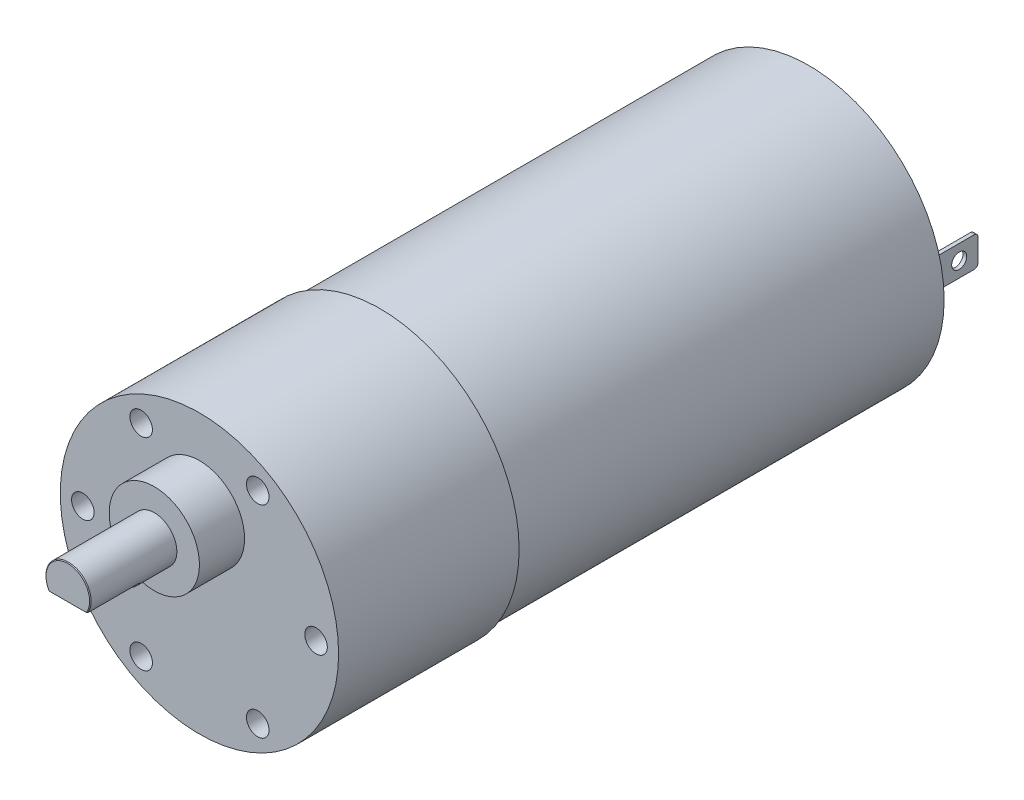
SolidWorks part; units mm, degrees
ref_plane "前视基准面" through (0, 0, 0) normal (0, 0, 1) x (1, 0, 0)
ref_plane "上视基准面" through (0, 0, 0) normal (0, 1, 0) x (1, 0, 0)
ref_plane "右视基准面" through (0, 0, 0) normal (1, 0, 0) x (0, 0, -1)
sketch "草图1" plane through (0, 0, 0) normal (0, 0, 1) x (1, 0, 0)
  circle A0 centre (0, 0) radius 18.5
  dimension "D1" = 37
extrude "凸台-拉伸1" add sketch "草图1" along normal blind 24
sketch "草图2" plane through (0, 0, 24) normal (0, 0, 1) x (1, 0, 0)
  circle A0 centre (0, 7) radius 6
  dimension "D2" = 12
  dimension "D1" = 7
extrude "凸台-拉伸2" add sketch "草图2" along normal blind 6
sketch "草图3" plane through (0, 0, 24) normal (0, 0, 1) x (1, 0, 0)
  circle A1 centre (15.5, 0) radius 1.5
  dimension "D1" = 3
  dimension "D2" = 15.5
extrude "切除-拉伸1" cut sketch "草图3" against normal blind 4
sketch "草图4" plane through (0, 0, 30) normal (0, 0, 1) x (1, 0, 0)
  circle A0 centre (0, 7) radius 3
  dimension "D1" = 6
extrude "凸台-拉伸3" add sketch "草图4" along normal blind 11.5
chamfer "倒角1" distance 0.1 angle 45 1 edges at (3, 7, 41.5)
sketch "草图5" plane through (0, 0, 41.5) normal (0, 0, 1) x (1, 0, 0)
  line L2 (-2.5897, 5.4856) -> (2.5897, 5.4856)
  circle A0 centre (0, 7) radius 3 construction
  arc A3 (-2.5897, 5.4856) -> (2.5897, 5.4856) centre (0, 7) ccw
extrude "切除-拉伸2" cut sketch "草图5" against normal blind 7
ref_axis "基准轴1" through (0, 0, 47.25) along (0, 0, -1)
pattern_circular "阵列(圆周)1" count 6 over 360 about axis through (0, 0, 47.25) along (0, 0, -1) of "切除-拉伸1"
sketch "草图6" plane through (0, 0, 0) normal (0, 0, -1) x (-1, 0, 0)
  circle A0 centre (0, 0) radius 18
  dimension "D1" = 36
extrude "凸台-拉伸4" add sketch "草图6" along normal blind 57
sketch "草图7" plane through (0, 0, -57) normal (0, 0, -1) x (-1, 0, 0)
  circle A0 centre (0, 0) radius 6.5
  dimension "D1" = 13
extrude "凸台-拉伸5" add sketch "草图7" along normal blind 3.5
fillet "圆角1" radius 1 1 edges at (-6.5, 0, -60.5)
sketch "草图8" plane through (0, 0, -60.5) normal (0, 0, -1) x (-1, 0, 0)
  circle A0 centre (0, 0) radius 1.5
  dimension "D1" = 3
extrude "凸台-拉伸6" add sketch "草图8" along normal blind 1
sketch "草图9" plane through (0, 0, -57) normal (0, 0, -1) x (-1, 0, 0)
  line L0 (14, 2) -> (14.5, 2)
  line L1 (14.5, 2) -> (14.5, -2)
  line L2 (14.5, -2) -> (14, -2)
  line L3 (14, -2) -> (14, 2)
  line L4 (-14, 2) -> (-14, -2)
  line L5 (-14, -2) -> (-14.5, -2)
  line L6 (-14.5, -2) -> (-14.5, 2)
  line L7 (-14.5, 2) -> (-14, 2)
  dimension "D1" = 0.5
  dimension "D2" = 0.5
  dimension "D3" = 4
  dimension "D4" = 2
  dimension "D5" = 4
  dimension "D6" = 2
  dimension "D7" = 14
  dimension "D8" = 14
extrude "凸台-拉伸7" add sketch "草图9" along normal blind 8
fillet "圆角2" radius 0.5 4 edges at (14.25, 2, -65) (14.25, -2, -65) (-14.25, -2, -65) (-14.25, 2, -65)
sketch "草图10" plane through (-14.5, 0, 0) normal (-1, 0, 0) x (0, 0, 1)
  line L0 (-65, -1.5) -> (-65, 1.5) construction
  circle A0 centre (-62.5, 0) radius 1
  point P2 (-65, 0)
  dimension "D1" = 2
  dimension "D2" = 2.5
extrude "切除-拉伸3" cut sketch "草图10" against normal blind 0.5
sketch "草图11" plane through (14.5, 0, 0) normal (1, 0, 0) x (0, 0, -1)
  line L0 (65, 1.5) -> (65, -1.5) construction
  circle A0 centre (62.5, 0) radius 1
  dimension "D1" = 2
  dimension "D2" = 2.5
extrude "切除-拉伸4" cut sketch "草图11" against normal blind 0.5
fillet "圆角3" radius 0.8 1 edges at (-1.5, 0, -61.5)
